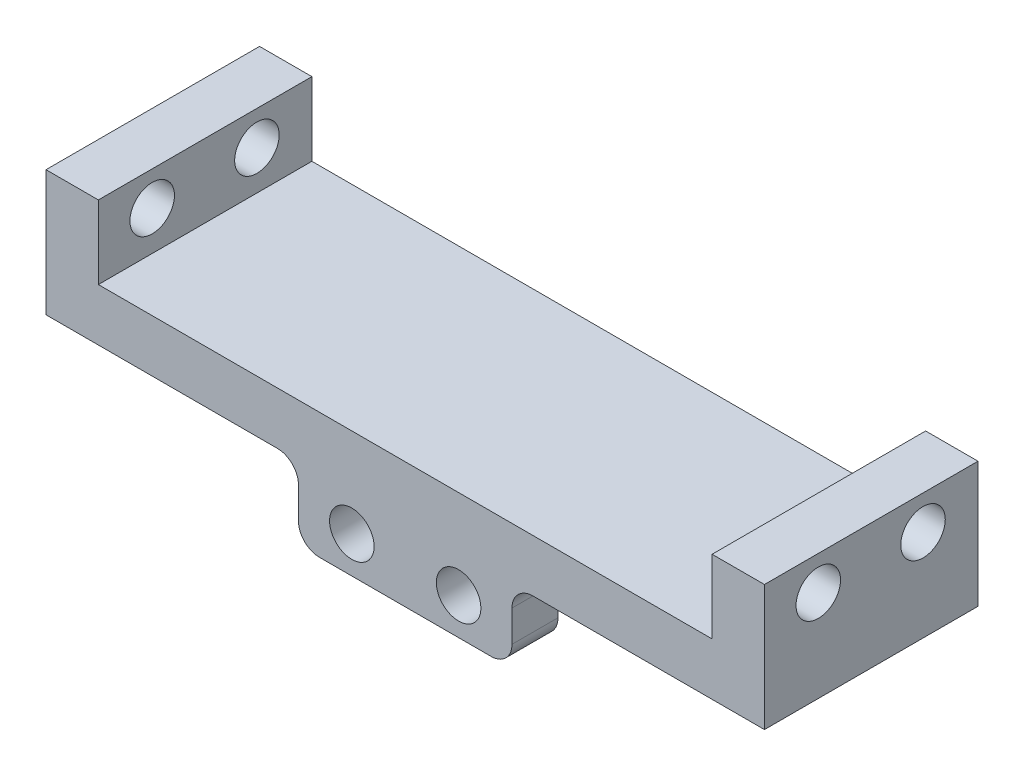
SolidWorks part; units mm, degrees
ref_plane "Front" through (0, 0, 0) normal (0, 0, 1) x (1, 0, 0)
ref_plane "Top" through (0, 0, 0) normal (0, 1, 0) x (1, 0, 0)
ref_plane "Right" through (0, 0, 0) normal (1, 0, 0) x (0, 0, -1)
sketch "Sketch1" plane through (0, 0, 0) normal (0, 1, 0) x (1, 0, 0)
  line L1 (0, 0) -> (68.6, 0)
  line L2 (0, 0) -> (0, 20.3898)
  line L3 (0, 20.3898) -> (68.6, 20.3898)
  line L4 (68.6, 0) -> (68.6, 20.3898)
  dimension "D1" = 68.6
  dimension "D2" = 20.3898
extrude "bracketBase" add sketch "Sketch1" along normal blind 5
sketch "Sketch2" plane through (0, 0, 0) normal (-1, 0, 0) x (0, 0, 1)
  line L0 (0, 5) -> (0, 0) construction
  line L1 (-20.3898, 0) -> (0, 0)
  line L2 (-20.3898, 0) -> (-20.3898, 12)
  line L3 (-20.3898, 12) -> (0, 12)
  line L4 (0, 0) -> (0, 12)
  line L5 (-20.3898, 5) -> (0, 5) construction
  dimension "D1" = 7
extrude "legMountingTab" add sketch "Sketch2" against normal blind 5
sketch "Sketch3" plane through (5, 0, 0) normal (1, 0, 0) x (0, 0, -1)
  line L0 (20.3898, 12) -> (20.3898, 5) construction
  line L1 (0, 12) -> (20.3898, 12) construction
  circle A0 centre (15.1398, 8.75) radius 2.125
  circle A1 centre (5.1398, 8.75) radius 2.125
  dimension "D1" = 4.25
  dimension "D2" = 5.25
  dimension "D3" = 3.25
  dimension "D4" = 10
extrude "legMountingHoles" cut sketch "Sketch3" against normal blind 5
ref_plane "Plane1" through (34.3, 0, 0) normal (-1, 0, 0) x (0, 0, 1)
mirror "legMountingHoles2" about plane through (34.3, 0, 0) normal (-1, 0, 0) of "legMountingHoles", "legMountingTab"
sketch "Sketch4" plane through (0, 0, 0) normal (0, 0, 1) x (1, 0, 0)
  line L0 (0, 0) -> (68.6, 0) construction
  line L1 (44.4949, 0) -> (24.1051, 0)
  line L2 (44.4949, 0) -> (44.4949, -7)
  line L3 (44.4949, -7) -> (24.1051, -7)
  line L4 (24.1051, 0) -> (24.1051, -7)
  point P4 (34.3, 0)
  point P7 (34.3, 0)
  dimension "D1" = 7
  dimension "D2" = 20.3898
extrude "arduinoMountingTab" add sketch "Sketch4" against normal blind 4.3898
sketch "Sketch5" plane through (0, 0, 0) normal (0, 0, 1) x (1, 0, 0)
  line L2 (34.3, -7) -> (34.3, 5) construction
  line L3 (24.1051, -7) -> (44.4949, -7) construction
  line L4 (5, 5) -> (63.6, 5) construction
  line L5 (44.4949, -3.5) -> (34.3, -3.5) construction
  line L8 (44.4949, -7) -> (44.4949, 0) construction
  circle A0 centre (39.3974, -3.5) radius 2.125
  circle A1 centre (29.2026, -3.5) radius 2.125
  dimension "D1" = 4.25
extrude "arduinoMountingHoles" cut sketch "Sketch5" against normal blind 5
fillet "Fillet1" radius 2 4 edges at (24.1051, -7, -2.1949) (44.4949, -7, -2.1949) (44.4949, 0, -2.1949) (24.1051, 0, -2.1949)
